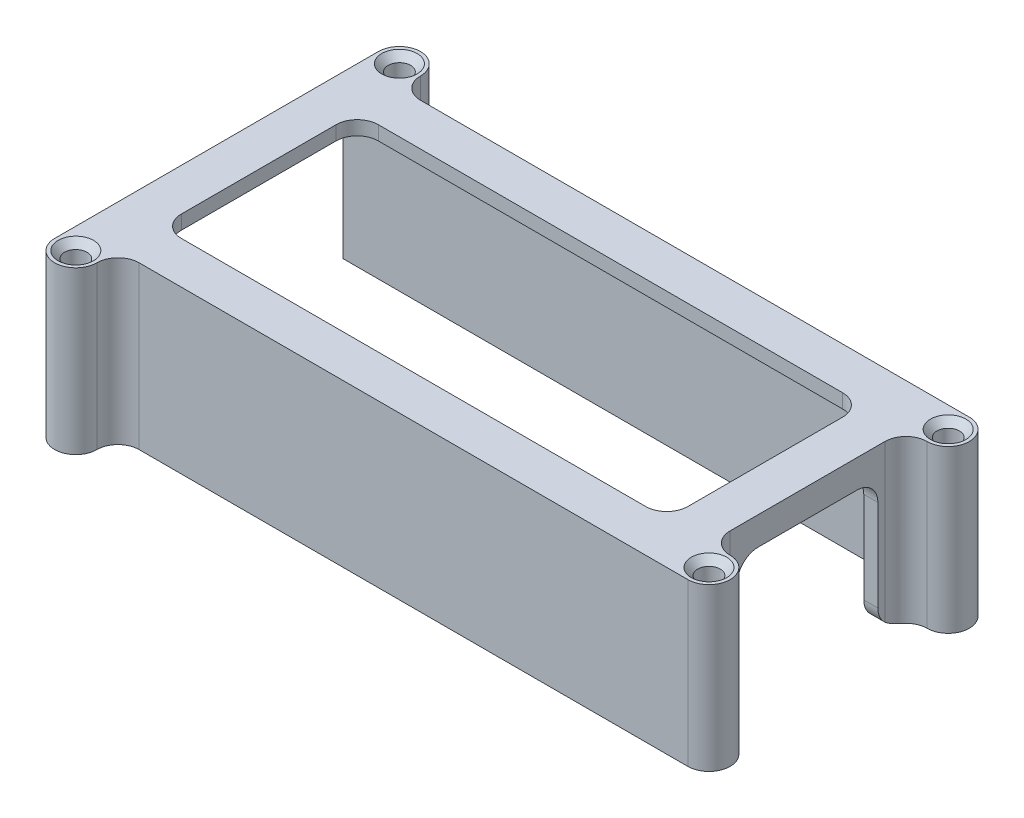
SolidWorks part; units mm, degrees
ref_plane "Front Plane" through (0, 0, 0) normal (0, 0, 1) x (1, 0, 0)
ref_plane "Top Plane" through (0, 0, 0) normal (0, 1, 0) x (1, 0, 0)
ref_plane "Right Plane" through (0, 0, 0) normal (1, 0, 0) x (0, 0, -1)
sketch "Sketch1" plane through (0, 0, 0) normal (0, 1, 0) x (1, 0, 0)
  line L0 (63.5, 28.575) -> (66.675, 31.75) construction
  line L1 (-63.5, -28.575) -> (63.5, -28.575)
  line L2 (-63.5, -28.575) -> (-63.5, 28.575)
  line L3 (-63.5, 28.575) -> (63.5, 28.575)
  line L4 (63.5, -28.575) -> (63.5, 28.575)
  line L5 (-63.5, -28.575) -> (63.5, 28.575) construction
  line L6 (-63.5, 28.575) -> (63.5, -28.575) construction
  line L7 (-66.675, -31.75) -> (66.675, -31.75)
  line L8 (-66.675, -31.75) -> (-66.675, 31.75)
  line L9 (-66.675, 31.75) -> (66.675, 31.75)
  line L10 (66.675, -31.75) -> (66.675, 31.75)
  line L11 (-66.675, -31.75) -> (66.675, 31.75) construction
  line L12 (-66.675, 31.75) -> (66.675, -31.75) construction
  line L13 (63.5, -28.575) -> (66.675, -31.75) construction
  point P0 (0, 0)
  point P6 (0, 0)
  dimension "D1" = 57.15
  dimension "D2" = 127
  dimension "D3" = 3.175
extrude "Boss-Extrude1" add sketch "Sketch1" along normal blind 33.3375
sketch "Sketch2" plane through (-66.675, 0, 0) normal (-1, 0, 0) x (0, 0, 1)
  line L0 (-31.75, 0) -> (31.75, 0) construction
  line L1 (-15.875, -30.1625) -> (15.875, -30.1625)
  line L2 (-15.875, -30.1625) -> (-15.875, 30.1625)
  line L3 (-15.875, 30.1625) -> (15.875, 30.1625)
  line L4 (15.875, -30.1625) -> (15.875, 30.1625)
  line L5 (-15.875, -30.1625) -> (15.875, 30.1625) construction
  line L6 (-15.875, 30.1625) -> (15.875, -30.1625) construction
  point P0 (0, 0)
  dimension "D1" = 31.75
  dimension "D2" = 30.1625
extrude "Cut-Extrude1" cut sketch "Sketch2" against normal through all
sketch "Sketch3" plane through (0, 33.3375, 0) normal (0, 1, 0) x (1, 0, 0)
  line L0 (-66.675, 31.75) -> (-57.15, 22.225) construction
  line L1 (57.15, -22.225) -> (-57.15, -22.225)
  line L2 (57.15, -22.225) -> (57.15, 22.225)
  line L3 (57.15, 22.225) -> (-57.15, 22.225)
  line L4 (66.675, -31.75) -> (66.675, 31.75)
  line L5 (66.675, 31.75) -> (-66.675, 31.75)
  line L6 (-66.675, 31.75) -> (-66.675, -31.75)
  line L7 (-66.675, -31.75) -> (66.675, -31.75)
  line L8 (66.675, -31.75) -> (66.675, 31.75)
  line L9 (66.675, 31.75) -> (-66.675, 31.75)
  line L10 (-66.675, 31.75) -> (-66.675, -31.75)
  line L11 (-66.675, -31.75) -> (66.675, -31.75)
  line L12 (-57.15, -22.225) -> (-57.15, 22.225)
  line L13 (57.15, -22.225) -> (-57.15, 22.225) construction
  line L14 (57.15, 22.225) -> (-57.15, -22.225) construction
  line L15 (-66.675, -31.75) -> (-57.15, -22.225) construction
  line L16 (63.5, 28.575) -> (-63.5, 28.575) construction
  point P2 (0, 0)
  dimension "D2" = 6.35
  dimension "D1" = 0
extrude "Boss-Extrude2" add sketch "Sketch3" along normal blind 3.175
sketch "Sketch4" plane through (0, 36.5125, 0) normal (0, 1, 0) x (1, 0, 0)
  line L0 (66.675, -31.75) -> (66.675, 31.75) construction
  line L1 (71.4375, 31.75) -> (66.675, 31.75)
  line L2 (66.675, 31.75) -> (66.675, 17.4625)
  circle A0 centre (71.4375, 26.9875) radius 1.27 construction
  arc A1 (71.4375, 31.75) -> (71.4375, 22.225) centre (71.4375, 26.9875) cw
  arc A2 (66.675, 17.4625) -> (71.4375, 22.225) centre (71.4375, 17.4625) cw
  dimension "D1" = 4.7625
  dimension "D2" = 2.54
extrude "Boss-Extrude3" add sketch "Sketch4" against normal up to surface (36.5125 mm away) up to face at (0, 0, -23.0187)
ref_axis "Axis1" through (71.4375, 0, -26.9875) along (0, 1, 0)
ref_plane "Plane1" through (71.4375, 0, 0) normal (1, 0, 0) x (0, 1, 0)
sketch "Sketch5" plane through (71.4375, 0, 0) normal (1, 0, 0) x (0, 1, 0)
  line L0 (0, -29.5275) -> (34.925, -29.5275)
  line L1 (34.925, -29.5275) -> (36.5125, -30.9822)
  line L2 (36.5125, -31.75) -> (36.5125, -22.225) construction
  line L3 (36.5125, -30.9822) -> (36.5125, -26.9875)
  line L4 (36.5125, -26.9875) -> (0, -26.9875) construction
  line L5 (0, -26.9875) -> (36.5125, -26.9875) construction
  line L6 (0, -26.9875) -> (0, -29.5275)
  line L7 (0, -22.225) -> (0, -31.75) construction
  line L8 (36.5125, -26.9875) -> (0, -26.9875)
  dimension "D1" = 5.08
  dimension "D2" = 42.5
  dimension "D3" = 1.5875
revolve "Cut-Revolve1" cut sketch "Sketch5" angle 360 about L8
sketch "Sketch6" plane through (0, 36.5125, 0) normal (0, 1, 0) x (1, 0, 0)
  line L0 (-66.675, 31.75) -> (-66.675, -31.75) construction
  line L1 (-66.675, 36.5125) -> (-66.675, 31.75)
  line L2 (-66.675, 31.75) -> (-52.3875, 31.75)
  line L3 (71.4375, 31.75) -> (-66.675, 31.75) construction
  circle A0 centre (-61.9125, 36.5125) radius 3.9947 construction
  arc A1 (-57.15, 36.5125) -> (-66.675, 36.5125) centre (-61.9125, 36.5125) ccw
  arc A2 (-52.3875, 31.75) -> (-57.15, 36.5125) centre (-52.3875, 36.5125) cw
  arc A3 (71.4375, 22.225) -> (71.4375, 31.75) centre (71.4375, 26.9875) ccw construction
  circle A5 centre (71.4375, 26.9875) radius 3.9947 construction
  arc A6 (-61.9125, 31.75) -> (-57.15, 36.5125) centre (-61.9125, 36.5125) ccw construction
  arc A7 (-66.675, 36.5125) -> (-61.9125, 31.75) centre (-61.9125, 36.5125) ccw construction
  circle A8 centre (-61.9125, 36.5125) radius 2.54
  circle A9 centre (71.4375, 26.9875) radius 2.54 construction
extrude "Boss-Extrude4" add sketch "Sketch6" against normal up to surface (36.5125 mm away) up to face at (71.4375, 0, -24.4475)
ref_axis "Axis2" through (-61.9125, 0, -36.5125) along (0, 1, 0)
ref_plane "Plane2" through (-61.9125, 0, 0) normal (-1, 0, 0) x (0, 1, 0)
sketch "Sketch7" plane through (-61.9125, 0, 0) normal (-1, 0, 0) x (0, 1, 0)
  line L0 (34.925, 39.0525) -> (36.5125, 40.5072)
  line L1 (0, 36.5125) -> (36.5125, 36.5125) construction
  line L2 (36.5125, 36.5125) -> (36.5125, 41.275) construction
  line L3 (36.5125, 40.5072) -> (36.5125, 36.5125)
  line L4 (36.5125, 33.9725) -> (36.5125, 39.0525) construction
  line L5 (36.5125, 36.5125) -> (34.925, 36.5125)
  line L6 (36.5125, 30.9822) -> (34.925, 29.5275) construction
  line L7 (34.925, 36.5125) -> (34.925, 39.0525)
  line L8 (32.1531, 36.5125) -> (34.925, 39.0525) construction
  line L9 (34.925, 36.5125) -> (32.1531, 36.5125) construction
  line L10 (36.5125, 26.9875) -> (36.5125, 30.9822) construction
  line L11 (0, 26.9875) -> (36.5125, 26.9875) construction
  line L12 (36.5125, 36.5125) -> (36.5125, -31.75) construction
  point P11 (34.925, 36.5125)
  point P21 (34.925, 36.4232)
revolve "Cut-Revolve2" cut sketch "Sketch7" angle 360 about L9
mirror "Mirror1" about plane through (0, 0, 0) normal (0, 0, 1) of "Cut-Revolve2", "Boss-Extrude4", "Boss-Extrude3", "Cut-Revolve1"
mirror "Mirror2" [suppressed] about plane through (0, 0, 0) normal (1, 0, 0)
sketch "Sketch8" plane through (-63.5, 0, 0) normal (1, 0, 0) x (0, 0, -1)
  line L8 (-15.875, 0) -> (-15.875, 30.1625)
  line L9 (-15.875, 30.1625) -> (15.875, 30.1625)
  line L10 (15.875, 30.1625) -> (15.875, 0)
  line L11 (15.875, 0) -> (28.575, 0)
  line L12 (28.575, 0) -> (28.575, 33.3375)
  line L13 (28.575, 33.3375) -> (-28.575, 33.3375)
  line L14 (-28.575, 33.3375) -> (-28.575, 0)
  line L15 (-28.575, 0) -> (-15.875, 0)
  line L16 (-15.875, 0) -> (-15.875, 30.1625)
  line L17 (-15.875, 30.1625) -> (15.875, 30.1625)
  line L18 (15.875, 30.1625) -> (15.875, 0)
  line L19 (15.875, 0) -> (28.575, 0)
  line L20 (28.575, 0) -> (28.575, 33.3375)
  line L21 (28.575, 33.3375) -> (-28.575, 33.3375)
  line L22 (-28.575, 33.3375) -> (-28.575, 0)
  line L23 (-28.575, 0) -> (-15.875, 0)
  dimension "D1" = 0
extrude "Cut-Extrude2" cut sketch "Sketch8" against normal through all
fillet "Fillet1" radius 1.5875 5 edges at (63.5, 16.6687, -28.575) (-1.5875, 33.3375, -28.575) (63.5, 16.6687, 28.575) (63.5, 33.3375, 0) (-1.5875, 33.3375, 28.575)
fillet "Fillet2" radius 4.7625 8 edges at (65.0875, 0, 15.875) (65.0875, 0, -15.875) (65.0875, 30.1625, -15.875) (65.0875, 30.1625, 15.875) (-57.15, 34.925, 22.225) (-57.15, 34.925, -22.225) (57.15, 34.925, 22.225) (57.15, 34.925, -22.225)
